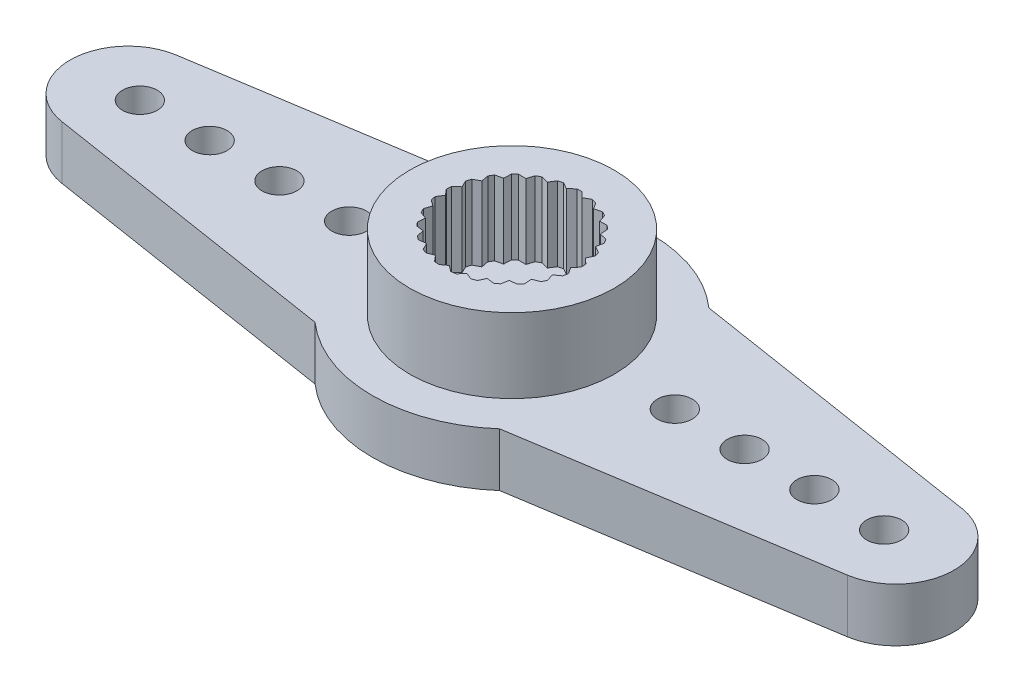
SolidWorks part; units mm, degrees
material "ABS"
ref_plane "Front Plane" through (0, 0, 0) normal (0, 0, 1) x (1, 0, 0)
ref_plane "Top Plane" through (0, 0, 0) normal (0, 1, 0) x (1, 0, 0)
ref_plane "Right Plane" through (0, 0, 0) normal (1, 0, 0) x (0, 0, -1)
sketch "Sketch2" plane through (0, 0, 0) normal (0, 1, 0) x (1, 0, 0)
  circle A0 centre (0, 0) radius 6
  circle A1 centre (0, 0) radius 1.5
  dimension "D1" = 12
  dimension "D2" = 3
extrude "Boss-Extrude1" add sketch "Sketch2" along normal mid plane 2.3
sketch "Sketch3" plane through (0, 1.15, 0) normal (0, 1, 0) x (1, 0, 0)
  line L0 (0, 0) -> (0, 2.9) construction
  line L3 (0, 0) -> (0.376, 2.9763) construction
  line L52 (0.1074, 2.898) -> (0.3384, 2.6787)
  line L53 (-0.1074, 2.898) -> (-0.3384, 2.6787)
  line L54 (0.8248, 2.7802) -> (0.9939, 2.5104)
  line L55 (0.6167, 2.8337) -> (0.3384, 2.6787)
  line L56 (1.4903, 2.4878) -> (1.587, 2.1843)
  line L57 (1.302, 2.5913) -> (0.9939, 2.5104)
  line L58 (2.0621, 2.039) -> (2.0804, 1.721)
  line L59 (1.9055, 2.1861) -> (1.587, 2.1843)
  line L60 (2.5044, 1.4621) -> (2.443, 1.1496)
  line L61 (2.3893, 1.6435) -> (2.0804, 1.721)
  line L62 (2.7894, 0.7934) -> (2.6522, 0.5059)
  line L63 (2.723, 0.9977) -> (2.443, 1.1496)
  line L64 (2.899, 0.0748) -> (2.6947, -0.1695)
  line L65 (2.8855, 0.2892) -> (2.6522, 0.5059)
  line L66 (2.8265, -0.6486) -> (2.5679, -0.8343)
  line L67 (2.8668, -0.4375) -> (2.6947, -0.1695)
  line L68 (2.5765, -1.3311) -> (2.2797, -1.4467)
  line L69 (2.6679, -1.1367) -> (2.5679, -0.8343)
  line L70 (2.1645, -1.93) -> (1.8483, -1.9682)
  line L71 (2.3014, -1.7645) -> (2.2797, -1.4467)
  line L72 (1.6165, -2.4077) -> (1.3007, -2.366)
  line L73 (1.7903, -2.2814) -> (1.8483, -1.9682)
  line L74 (0.967, -2.734) -> (0.6715, -2.6152)
  line L75 (1.1667, -2.655) -> (1.3007, -2.366)
  line L76 (0.2566, -2.8886) -> (0, -2.7)
  line L77 (0.4698, -2.8617) -> (0.6715, -2.6152)
  line L78 (-0.4698, -2.8617) -> (-0.6715, -2.6152)
  line L79 (-0.2566, -2.8886) -> (0, -2.7)
  line L80 (-1.1667, -2.655) -> (-1.3007, -2.366)
  line L81 (-0.967, -2.734) -> (-0.6715, -2.6152)
  line L82 (-1.7903, -2.2814) -> (-1.8483, -1.9682)
  line L83 (-1.6165, -2.4077) -> (-1.3007, -2.366)
  line L84 (-2.3014, -1.7645) -> (-2.2797, -1.4467)
  line L85 (-2.1645, -1.93) -> (-1.8483, -1.9682)
  line L86 (-2.6679, -1.1367) -> (-2.5679, -0.8343)
  line L87 (-2.5765, -1.3311) -> (-2.2797, -1.4467)
  line L88 (-2.8668, -0.4375) -> (-2.6947, -0.1695)
  line L89 (-2.8265, -0.6486) -> (-2.5679, -0.8343)
  line L90 (-2.8855, 0.2892) -> (-2.6522, 0.5059)
  line L91 (-2.899, 0.0748) -> (-2.6947, -0.1695)
  line L92 (-2.723, 0.9977) -> (-2.443, 1.1496)
  line L93 (-2.7894, 0.7934) -> (-2.6522, 0.5059)
  line L94 (-2.3893, 1.6435) -> (-2.0804, 1.721)
  line L95 (-2.5044, 1.4621) -> (-2.443, 1.1496)
  line L96 (-1.9055, 2.1861) -> (-1.587, 2.1843)
  line L97 (-2.0621, 2.039) -> (-2.0804, 1.721)
  line L98 (-1.302, 2.5913) -> (-0.9939, 2.5104)
  line L99 (-1.4903, 2.4878) -> (-1.587, 2.1843)
  line L100 (-0.6167, 2.8337) -> (-0.3384, 2.6787)
  line L101 (-0.8248, 2.7802) -> (-0.9939, 2.5104)
  line L102 (-2.533, 1.6075) -> (-2.3893, 1.6435) construction
  line L103 (-2.533, 1.6075) -> (-2.5044, 1.4621) construction
  line L104 (-2.8532, 0.9271) -> (-2.723, 0.9977) construction
  line L105 (-2.8532, 0.9271) -> (-2.7894, 0.7934) construction
  line L106 (-2.9941, 0.1884) -> (-2.8855, 0.2892) construction
  line L107 (-2.9941, 0.1884) -> (-2.899, 0.0748) construction
  line L108 (-2.9469, -0.5621) -> (-2.8668, -0.4375) construction
  line L109 (-2.9469, -0.5621) -> (-2.8265, -0.6486) construction
  line L110 (0, 3) -> (0.1074, 2.898) construction
  line L111 (0, 2.9) -> (0, 3) construction
  line L112 (0, 3) -> (-0.1074, 2.898) construction
  line L113 (-0.7461, 2.9057) -> (-0.6167, 2.8337) construction
  line L114 (-0.7461, 2.9057) -> (-0.8248, 2.7802) construction
  line L115 (-1.4453, 2.6289) -> (-1.302, 2.5913) construction
  line L116 (-1.4453, 2.6289) -> (-1.4903, 2.4878) construction
  line L117 (-2.0536, 2.1869) -> (-1.9055, 2.1861) construction
  line L118 (-2.0536, 2.1869) -> (-2.0621, 2.039) construction
  line L119 (-2.7145, -1.2773) -> (-2.6679, -1.1367) construction
  line L120 (-2.7145, -1.2773) -> (-2.5765, -1.3311) construction
  line L121 (-2.3115, -1.9123) -> (-2.3014, -1.7645) construction
  line L122 (-2.3115, -1.9123) -> (-2.1645, -1.93) construction
  line L123 (-1.7634, -2.4271) -> (-1.7903, -2.2814) construction
  line L124 (-1.7634, -2.4271) -> (-1.6165, -2.4077) construction
  line L125 (-1.1044, -2.7893) -> (-1.1667, -2.655) construction
  line L126 (-1.1044, -2.7893) -> (-0.967, -2.734) construction
  line L127 (-0.376, -2.9763) -> (-0.4698, -2.8617) construction
  line L128 (-0.376, -2.9763) -> (-0.2566, -2.8886) construction
  line L129 (0.376, -2.9763) -> (0.2566, -2.8886) construction
  line L130 (0.376, -2.9763) -> (0.4698, -2.8617) construction
  line L131 (1.1044, -2.7893) -> (0.967, -2.734) construction
  line L132 (1.1044, -2.7893) -> (1.1667, -2.655) construction
  line L133 (1.7634, -2.4271) -> (1.6165, -2.4077) construction
  line L134 (1.7634, -2.4271) -> (1.7903, -2.2814) construction
  line L135 (2.3115, -1.9123) -> (2.3014, -1.7645) construction
  line L136 (2.3115, -1.9123) -> (2.1645, -1.93) construction
  line L137 (2.7145, -1.2773) -> (2.6679, -1.1367) construction
  line L138 (2.7145, -1.2773) -> (2.5765, -1.3311) construction
  line L139 (2.9469, -0.5621) -> (2.8668, -0.4375) construction
  line L140 (2.9469, -0.5621) -> (2.8265, -0.6486) construction
  line L141 (2.9941, 0.1884) -> (2.8855, 0.2892) construction
  line L142 (2.9941, 0.1884) -> (2.899, 0.0748) construction
  line L143 (2.8532, 0.9271) -> (2.723, 0.9977) construction
  line L144 (2.8532, 0.9271) -> (2.7894, 0.7934) construction
  line L145 (2.533, 1.6075) -> (2.3893, 1.6435) construction
  line L146 (2.533, 1.6075) -> (2.5044, 1.4621) construction
  line L147 (2.0536, 2.1869) -> (1.9055, 2.1861) construction
  line L148 (2.0536, 2.1869) -> (2.0621, 2.039) construction
  line L149 (1.4453, 2.6289) -> (1.302, 2.5913) construction
  line L150 (1.4453, 2.6289) -> (1.4903, 2.4878) construction
  line L151 (0.7461, 2.9057) -> (0.6167, 2.8337) construction
  line L152 (0.7461, 2.9057) -> (0.8248, 2.7802) construction
  circle A0 centre (0, 0) radius 4.4
  circle A1 centre (0, 0) radius 3 construction
  circle A2 centre (0, 0) radius 2.7 construction
  arc A3 (-0.6167, 2.8337) -> (-0.8248, 2.7802) centre (0, 0) ccw
  arc A4 (-0.1074, 2.898) -> (-0.6167, 2.8337) centre (0, 0) ccw construction
  arc A5 (-0.8248, 2.7802) -> (-1.302, 2.5913) centre (0, 0) ccw construction
  arc A6 (-1.302, 2.5913) -> (-1.4903, 2.4878) centre (0, 0) ccw
  arc A7 (-1.4903, 2.4878) -> (-1.9055, 2.1861) centre (0, 0) ccw construction
  arc A8 (-1.9055, 2.1861) -> (-2.0621, 2.039) centre (0, 0) ccw
  arc A9 (-2.0621, 2.039) -> (-2.3893, 1.6435) centre (0, 0) ccw construction
  arc A10 (-2.3893, 1.6435) -> (-2.5044, 1.4621) centre (0, 0) ccw
  arc A11 (-2.5044, 1.4621) -> (-2.723, 0.9977) centre (0, 0) ccw construction
  arc A12 (-2.723, 0.9977) -> (-2.7894, 0.7934) centre (0, 0) ccw
  arc A13 (-2.7894, 0.7934) -> (-2.8855, 0.2892) centre (0, 0) ccw construction
  arc A14 (-2.8855, 0.2892) -> (-2.899, 0.0748) centre (0, 0) ccw
  arc A15 (-2.899, 0.0748) -> (-2.8668, -0.4375) centre (0, 0) ccw construction
  arc A16 (-2.8668, -0.4375) -> (-2.8265, -0.6486) centre (0, 0) ccw
  arc A17 (-2.8265, -0.6486) -> (-2.6679, -1.1367) centre (0, 0) ccw construction
  arc A18 (-2.6679, -1.1367) -> (-2.5765, -1.3311) centre (0, 0) ccw
  arc A19 (-2.5765, -1.3311) -> (-2.3014, -1.7645) centre (0, 0) ccw construction
  arc A20 (-2.3014, -1.7645) -> (-2.1645, -1.93) centre (0, 0) ccw
  arc A21 (-2.1645, -1.93) -> (-1.7903, -2.2814) centre (0, 0) ccw construction
  arc A22 (-1.7903, -2.2814) -> (-1.6165, -2.4077) centre (0, 0) ccw
  arc A23 (-1.6165, -2.4077) -> (-1.1667, -2.655) centre (0, 0) ccw construction
  arc A24 (-1.1667, -2.655) -> (-0.967, -2.734) centre (0, 0) ccw
  arc A25 (-0.967, -2.734) -> (-0.4698, -2.8617) centre (0, 0) ccw construction
  arc A26 (-0.4698, -2.8617) -> (-0.2566, -2.8886) centre (0, 0) ccw
  arc A27 (-0.2566, -2.8886) -> (0.2566, -2.8886) centre (0, 0) ccw construction
  arc A28 (0.2566, -2.8886) -> (0.4698, -2.8617) centre (0, 0) ccw
  arc A29 (0.4698, -2.8617) -> (0.967, -2.734) centre (0, 0) ccw construction
  arc A30 (0.967, -2.734) -> (1.1667, -2.655) centre (0, 0) ccw
  arc A31 (1.1667, -2.655) -> (1.6165, -2.4077) centre (0, 0) ccw construction
  arc A32 (1.6165, -2.4077) -> (1.7903, -2.2814) centre (0, 0) ccw
  arc A33 (1.7903, -2.2814) -> (2.1645, -1.93) centre (0, 0) ccw construction
  arc A34 (2.1645, -1.93) -> (2.3014, -1.7645) centre (0, 0) ccw
  arc A35 (2.3014, -1.7645) -> (2.5765, -1.3311) centre (0, 0) ccw construction
  arc A36 (2.5765, -1.3311) -> (2.6679, -1.1367) centre (0, 0) ccw
  arc A37 (2.6679, -1.1367) -> (2.8265, -0.6486) centre (0, 0) ccw construction
  arc A38 (2.8265, -0.6486) -> (2.8668, -0.4375) centre (0, 0) ccw
  arc A39 (2.8668, -0.4375) -> (2.899, 0.0748) centre (0, 0) ccw construction
  arc A40 (2.899, 0.0748) -> (2.8855, 0.2892) centre (0, 0) ccw
  arc A41 (2.8855, 0.2892) -> (2.7894, 0.7934) centre (0, 0) ccw construction
  arc A42 (2.7894, 0.7934) -> (2.723, 0.9977) centre (0, 0) ccw
  arc A43 (2.723, 0.9977) -> (2.5044, 1.4621) centre (0, 0) ccw construction
  arc A44 (2.5044, 1.4621) -> (2.3893, 1.6435) centre (0, 0) ccw
  arc A45 (2.3893, 1.6435) -> (2.0621, 2.039) centre (0, 0) ccw construction
  arc A46 (2.0621, 2.039) -> (1.9055, 2.1861) centre (0, 0) ccw
  arc A47 (1.9055, 2.1861) -> (1.4903, 2.4878) centre (0, 0) ccw construction
  arc A48 (1.4903, 2.4878) -> (1.302, 2.5913) centre (0, 0) ccw
  arc A49 (1.302, 2.5913) -> (0.8248, 2.7802) centre (0, 0) ccw construction
  arc A50 (0.8248, 2.7802) -> (0.6167, 2.8337) centre (0, 0) ccw
  arc A51 (0.3635, 2.8771) -> (0.1074, 2.898) centre (0, 0) ccw construction
  arc A52 (0.1074, 2.898) -> (-0.1074, 2.898) centre (0, 0) ccw
  arc A53 (0.6167, 2.8337) -> (0.3635, 2.8771) centre (0, 0) ccw construction
  point P84 (0, 0)
  dimension "D1" = 8.8
  dimension "D2" = 5.4
  dimension "D3" = 6
  dimension "D6" = 5.8
  dimension "D4" = 7.2
  dimension "D5" = 25
extrude "Boss-Extrude2" add sketch "Sketch3" along normal blind 3.2
sketch "Sketch4" plane through (0, 0, 0) normal (0, 1, 0) x (1, 0, 0)
  line L0 (0, 0) -> (16, 0) construction
  line L1 (3.9686, 4.5) -> (16.8881, 2.4697)
  line L2 (3.9686, -4.5) -> (16.8881, -2.4697)
  line L3 (16, 0) -> (13, 0) construction
  circle A0 centre (0, 0) radius 6 construction
  arc A1 (3.9686, -4.5) -> (3.9686, 4.5) centre (0, 0) ccw
  arc A2 (16.8881, 2.4697) -> (16.8881, -2.4697) centre (16.5, 0) cw
  circle A3 centre (16, 0) radius 0.75
  circle A4 centre (13, 0) radius 0.75
  circle A5 centre (10, 0) radius 0.75
  circle A6 centre (7, 0) radius 0.75
  dimension "D3" = 2.5
  dimension "D5" = 1.5
  dimension "D2" = 9
  dimension "D7" = 3
  dimension "D4" = 0.5
  dimension "D1" = 16
  dimension "D6" = 4
extrude "Boss-Extrude3" add sketch "Sketch4" along normal mid plane 2.3
pattern_circular "CirPattern1" count 2 over 360 about axis through (0, 4.35, 0) along (0, 1, 0) of "Boss-Extrude3"
sketch "Sketch5" plane through (0, 0, 0) normal (0, 1, 0) x (1, 0, 0)
  line L0 (3, 7) -> (-3, 7) construction
  circle A0 centre (0, 0) radius 10
  circle A1 centre (0, 7) radius 0.75
  circle A2 centre (-3, 7) radius 0.75
  circle A3 centre (3, 7) radius 0.75
  circle A4 centre (7, 3) radius 0.75
  circle A5 centre (7, 0) radius 0.75
  circle A6 centre (7, -3) radius 0.75
  circle A7 centre (3, -7) radius 0.75
  circle A8 centre (0, -7) radius 0.75
  circle A9 centre (-3, -7) radius 0.75
  circle A10 centre (-7, -3) radius 0.75
  circle A11 centre (-7, 0) radius 0.75
  circle A12 centre (-7, 3) radius 0.75
  circle A13 centre (0, 0) radius 1.5 construction
  circle A14 centre (0, 0) radius 1.5
  point P8 (0, 7)
  point P31 (0, 0)
  dimension "D1" = 1.5
  dimension "D3" = 2.25
  dimension "D4" = 6
  dimension "D2" = 7
  dimension "D5" = 4
extrude "Boss-Extrude4" [suppressed] add sketch "Sketch5" along normal mid plane 2.3
sketch "Sketch6" plane through (0, 1.15, 0) normal (0, 1, 0) x (1, 0, 0)
  line L0 (-16.8881, 2.4697) -> (-3.9686, 4.5)
  line L1 (-16.8881, -2.4697) -> (-3.9686, -4.5)
  line L2 (3.9686, 4.5) -> (16.8881, 2.4697)
  line L3 (16.8881, -2.4697) -> (3.9686, -4.5)
  arc A0 (-16.8881, 2.4697) -> (-16.8881, -2.4697) centre (-16.5, 0) ccw
  arc A1 (-3.9686, 4.5) -> (3.9686, 4.5) centre (0, 0) cw
  arc A2 (-3.9686, -4.5) -> (3.9686, -4.5) centre (0, 0) ccw
  arc A3 (16.8881, -2.4697) -> (16.8881, 2.4697) centre (16.5, 0) ccw
equation "\"N_hole\"= 4"
equation "\"N_horn\"= 2"
equation "\"D6@Sketch4\"=\"N_hole\""
equation "\"D1@CirPattern1\"=\"N_horn\""
equation "\"D1@Sketch4\"=(\"N_hole\" - 1) *3 +7"
